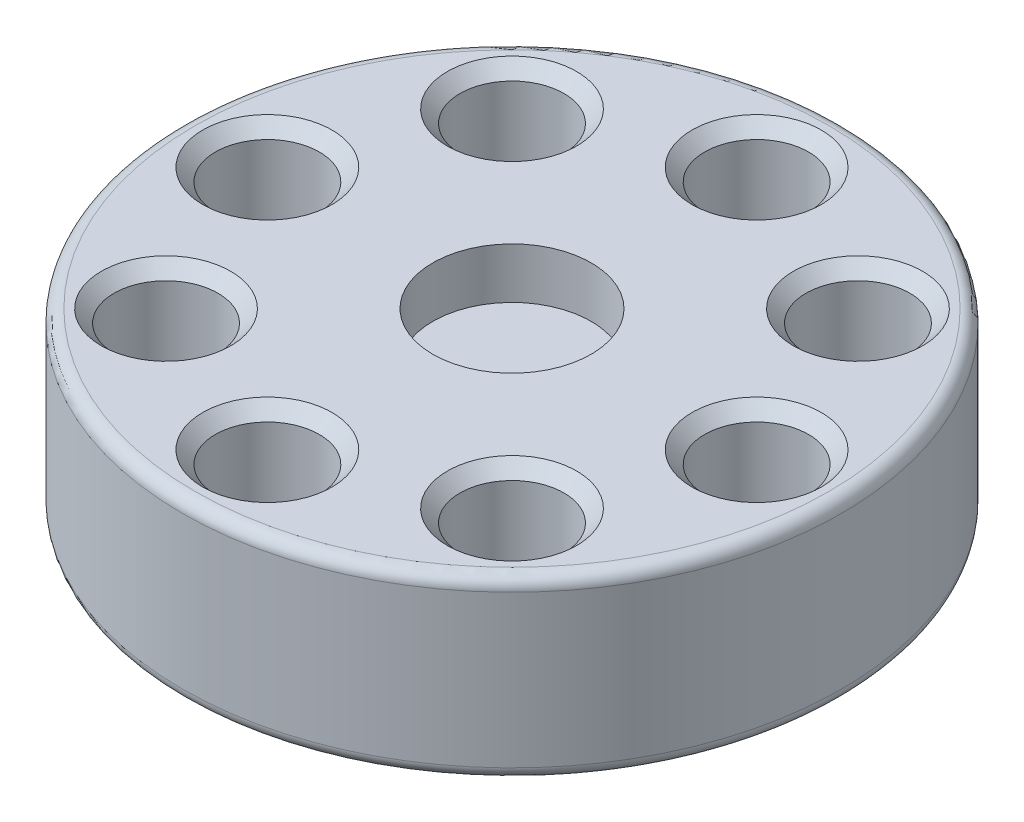
SolidWorks part; units mm, degrees
ref_plane "Front Plane" through (0, 0, 0) normal (0, 0, 1) x (1, 0, 0)
ref_plane "Top Plane" through (0, 0, 0) normal (0, 1, 0) x (1, 0, 0)
ref_plane "Right Plane" through (0, 0, 0) normal (1, 0, 0) x (0, 0, -1)
sketch "Sketch1" plane through (0, 0, 0) normal (0, 1, 0) x (1, 0, 0)
  circle A0 centre (0, 0) radius 26
  circle A1 centre (-13.6472, 13.6472) radius 4.1
  circle A2 centre (0, 19.3) radius 4.1
  circle A3 centre (13.6472, 13.6472) radius 4.1
  circle A4 centre (19.3, 0) radius 4.1
  circle A5 centre (13.6472, -13.6472) radius 4.1
  circle A6 centre (0, -19.3) radius 4.1
  circle A7 centre (-13.6472, -13.6472) radius 4.1
  circle A8 centre (-19.3, 0) radius 4.1
  circle A9 centre (0, 0) radius 6.25
  point P5 (0, 0)
  circle B0 centre (0, 19.3) radius 4.1
  circle B1 centre (13.6472, 13.6472) radius 4.1
  circle B2 centre (0, 0) radius 6.25
  circle B3 centre (-13.6472, 13.6472) radius 4.1
  circle B4 centre (-19.3, 0) radius 4.1
  circle B5 centre (-13.6472, -13.6472) radius 4.1
  circle B6 centre (0, -19.3) radius 4.1
  circle B7 centre (13.6472, -13.6472) radius 4.1
  circle B8 centre (19.3, 0) radius 4.1
sketch_block_instance "Block2-9"
sketch_block "Block2" parameters "D2"=3.9779, "D1"=8
extrude "Boss-Extrude1" add sketch "Sketch1" along normal blind 14 contours A0
sketch "Sketch2" plane through (0, 0, 0) normal (0, -1, 0) x (1, 0, 0)
  circle A1 centre (0, 0) radius 6.1
extrude "Cut-Extrude2" cut sketch "Sketch2" against normal blind 4
extrude "Cut-Extrude5" cut sketch "Sketch1<9>" against normal blind 4 from surface contours A9 starting at face at (0, 14, 26)
sketch "Sketch1<9>" plane through (0, 0, 0) normal (0, 1, 0) x (1, 0, 0) same geometry as "Sketch1"
extrude "Cut-Extrude6" cut sketch "Sketch1<13>" along normal blind 8 contours A6 | A5 | A4 | A3 | A2 | A1 | A8 | A7
sketch "Sketch1<13>" plane through (0, 0, 0) normal (0, 1, 0) x (1, 0, 0) same geometry as "Sketch1"
extrude "Cut-Extrude7" cut sketch "Sketch1<15>" against normal through all from surface contours A3 | A4 | A5 | A6 | A2 | A1 | A8 | A7 starting at face at (0, 14, 6.25)
sketch "Sketch1<15>" plane through (0, 0, 0) normal (0, 1, 0) x (1, 0, 0) same geometry as "Sketch1"
fillet "Fillet3" radius 1 2 edges at (0, 0, 26) (0, 14, 26)
chamfer "Chamfer1" distance 1 angle 45 16 edges at (13.6472, 14, 17.7472) (13.6472, 0, 17.7472) (0, 14, 23.4) (0, 0, 23.4) (-13.6472, 14, 17.7472) (-13.6472, 0, 17.7472) (0, 14, -15.2) (0, 0, -15.2) (-19.3, 14, 4.1) (-13.6472, 14, -9.5472) (13.6472, 14, -9.5472) (19.3, 14, 4.1) (-19.3, 0, 4.1) (-13.6472, 0, -9.5472) (13.6472, 0, -9.5472) (19.3, 0, 4.1)
